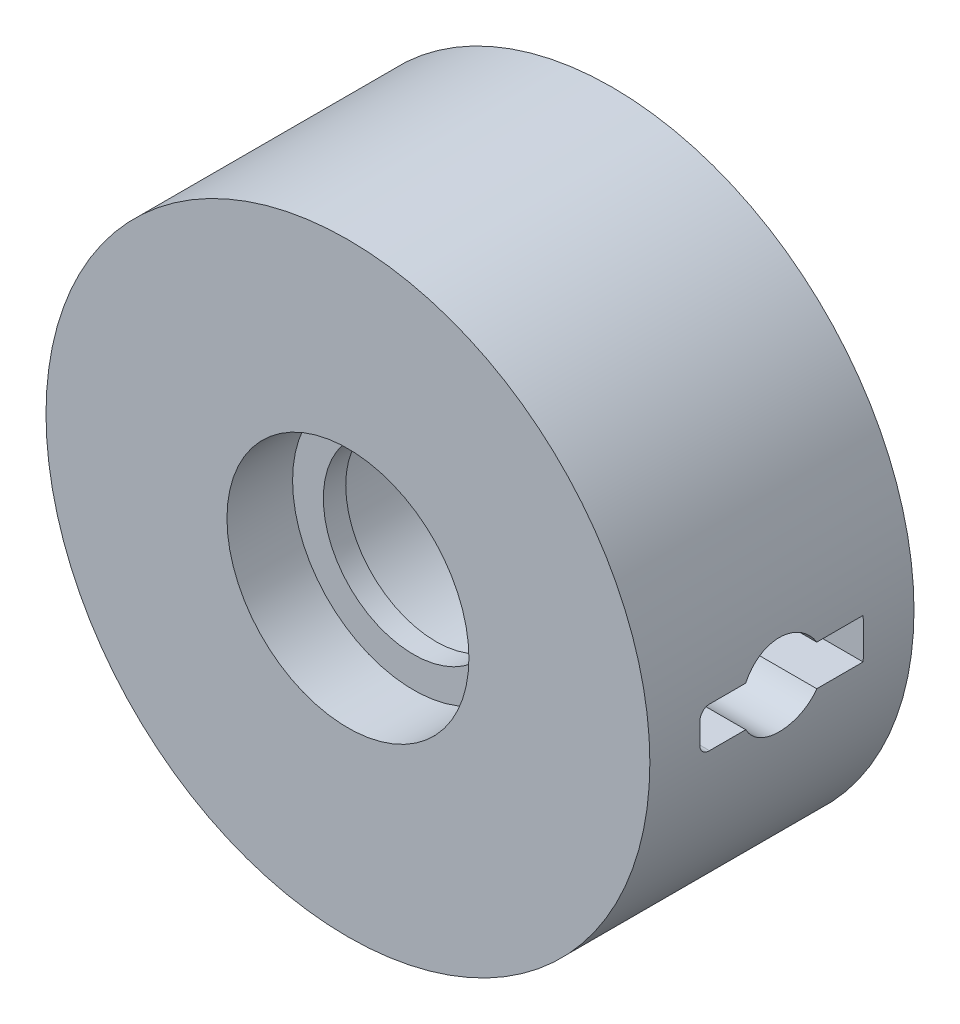
SolidWorks part; units mm, degrees
ref_plane "Front Plane" through (0, 0, 0) normal (0, 0, 1) x (1, 0, 0)
ref_plane "Top Plane" through (0, 0, 0) normal (0, 1, 0) x (1, 0, 0)
ref_plane "Right Plane" through (0, 0, 0) normal (1, 0, 0) x (0, 0, -1)
sketch "Sketch1" plane through (0, 0, 0) normal (0, 0, 1) x (1, 0, 0)
  circle A0 centre (0, 0) radius 29.95
  dimension "D1" = 59.9
extrude "Boss-Extrude1" add sketch "Sketch1" along normal blind 12.7
sketch "Sketch3" plane through (0, 0, 0) normal (0, 0, -1) x (-1, 0, 0)
  circle A0 centre (0, 0) radius 12
  dimension "D1" = 24
extrude "Cut-Extrude2" cut sketch "Sketch3" against normal through all
ref_plane "Plane1" through (0, 0, 3.9688) normal (0, 0, -1) x (-1, 0, 0)
sketch "Sketch4" plane through (0, 0, 3.9688) normal (0, 0, -1) x (-1, 0, 0)
  circle A1 centre (0, 0) radius 12
  dimension "D1" = 24
extrude "Boss-Extrude2" add sketch "Sketch4" against normal blind 2.2225
sketch "Sketch5" plane through (0, 0, 6.1913) normal (0, 0, 1) x (1, 0, 0)
  circle A0 centre (0, 0) radius 8.95
  dimension "D1" = 17.9
extrude "Cut-Extrude3" cut sketch "Sketch5" against normal through all
ref_point "Point1"
sketch "Sketch11" plane through (0, 0, 0) normal (0, 0, -1) x (-1, 0, 0)
  circle A0 centre (0, 0) radius 12 construction
  circle A1 centre (0, 0) radius 29.95 construction
  circle A2 centre (0, 0) radius 12
  circle A3 centre (0, 0) radius 29.95
extrude "Boss-Extrude6" add sketch "Sketch11" along normal blind 13.5
ref_plane "Plane2" through (-29.95, 0, 6.1913) normal (-1, 0, 0) x (0, 0, 1)
sketch "Sketch12" plane through (-29.95, 0, 6.1913) normal (-1, 0, 0) x (0, 0, 1)
  line L0 (-19.6913, 29.95) -> (-19.6913, -29.95) construction
  line L1 (6.5088, -29.95) -> (6.5088, 29.95) construction
  line L2 (-19.6913, 29.95) -> (-19.6913, -29.95) construction
  line L3 (6.5088, -29.95) -> (6.5088, 29.95) construction
  line L4 (6.5088, 0) -> (-19.6913, 0) construction
  line L5 (6.5088, 29.95) -> (-19.6913, 29.95) construction
  line L6 (-19.6913, -29.95) -> (6.5088, -29.95) construction
  line L7 (6.5088, 29.95) -> (-19.6913, 29.95) construction
  line L8 (-19.6913, -29.95) -> (6.5088, -29.95) construction
  line L9 (-6.5913, -29.95) -> (-6.5912, 29.95) construction
  circle A0 centre (-6.5912, 0) radius 4.05
  dimension "D1" = 8.1
extrude "Cut-Extrude4" cut sketch "Sketch12" against normal blind 14.5
ref_plane "Plane3" through (-16.95, 0, 6.1913) normal (-1, 0, 0) x (0, 0, 1)
sketch "Sketch14" plane through (-16.95, 0, 6.1913) normal (-1, 0, 0) x (0, 0, 1)
  circle A0 centre (-6.5912, 0) radius 4.05 construction
  circle A1 centre (-6.5912, 0) radius 4.05
extrude "Boss-Extrude7" add sketch "Sketch14" along normal blind 4
sketch "Sketch16" plane through (-20.95, 0, 0) normal (-1, 0, 0) x (0, 0, 1)
  circle A0 centre (-0.4, 0) radius 4.05 construction
  circle A1 centre (-0.4, 0) radius 4.05 construction
  circle A2 centre (-0.4, 0) radius 3
  dimension "D1" = 6
extrude "Cut-Extrude5" cut sketch "Sketch16" against normal blind 4
sketch "Sketch17" plane through (-29.95, 0, 6.1913) normal (-1, 0, 0) x (0, 0, 1)
  line L0 (0.5305, 2) -> (-3.0695, 2)
  line L1 (-6.5912, 0) -> (-6.5912, -5.109) construction
  line L8 (1.5305, 2) -> (-1.1815, -0.5) construction
  line L13 (-14.713, -2) -> (-10.113, -2)
  line L14 (-14.713, -2) -> (-14.713, 2)
  line L15 (1.5305, -1) -> (1.5305, 1)
  line L16 (0.5305, -2) -> (-3.0695, -2)
  line L19 (-14.713, 2) -> (-10.113, 2)
  line L21 (-14.713, -2) -> (-12.001, -0.5) construction
  line L22 (-14.713, 2) -> (-12.001, -0.5) construction
  line L24 (1.5305, -2) -> (-1.1815, -0.5) construction
  circle A0 centre (-6.5912, 0) radius 4.05 construction
  arc A5 (0.5305, 2) -> (1.5305, 1) centre (0.5305, 1) cw
  arc A7 (-10.113, 2) -> (-10.113, -2) centre (-6.5912, 0) ccw
  arc A8 (-3.0695, 2) -> (-3.0695, -2) centre (-6.5912, 0) cw
  arc A9 (1.5305, -1) -> (0.5305, -2) centre (0.5305, -1) cw
  point P1 (-12.001, -0.5)
  point P10 (0, 0)
  dimension "D3" = 3.6885
  dimension "D5" = 1
  dimension "D2" = 4.6
  dimension "D4" = 2.712
  dimension "D10" = 4
extrude "Cut-Extrude6" cut sketch "Sketch17" against normal blind 8
ref_axis "Axis1" through (0, 0, 3.9688) along (0, 0, -1)
ref_plane "Plane4" through (0, 0, 0) normal (-1, 0, 0) x (0, 0, 1)
mirror "Mirror1" about plane through (0, 0, 0) normal (-1, 0, 0) of "Cut-Extrude4", "Boss-Extrude7", "Cut-Extrude5", "Cut-Extrude6"
